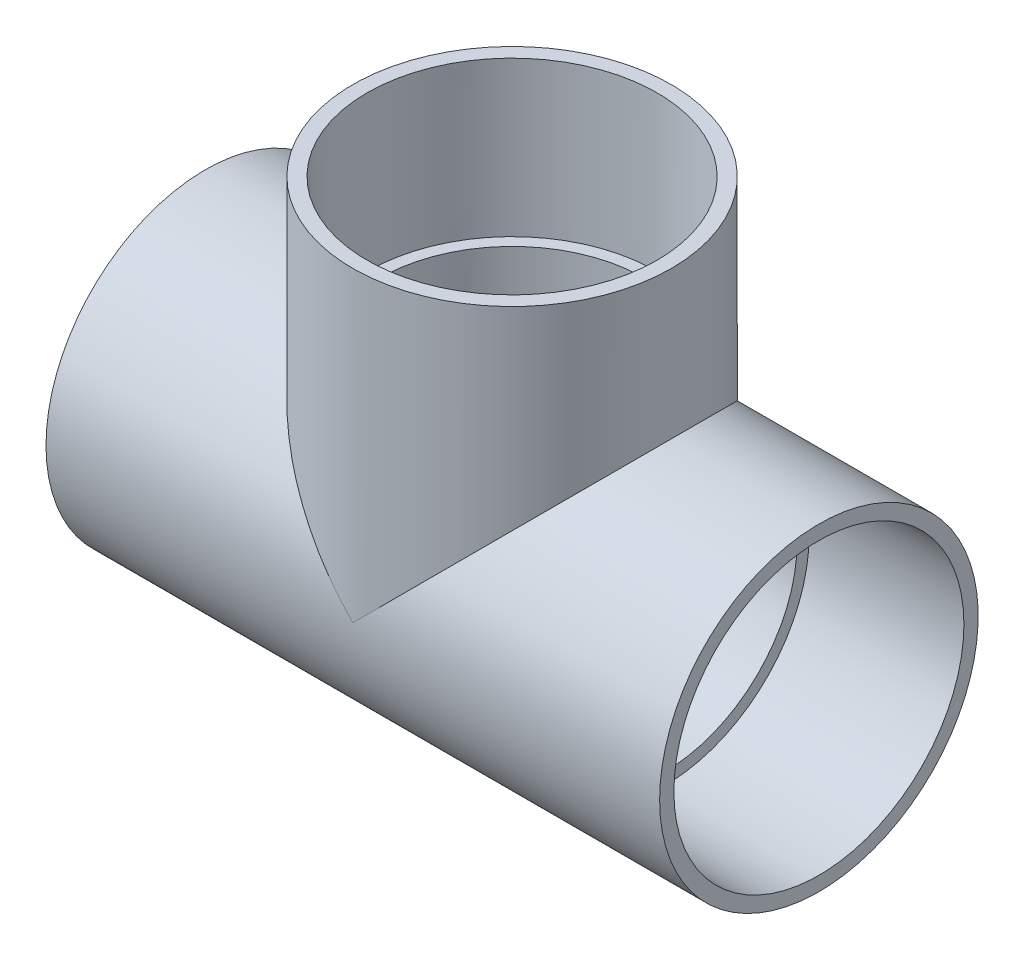
SolidWorks part; units mm, degrees
ref_plane "Front Plane" through (0, 0, 0) normal (0, 0, 1) x (1, 0, 0)
ref_plane "Top Plane" through (0, 0, 0) normal (0, 1, 0) x (1, 0, 0)
ref_plane "Right Plane" through (0, 0, 0) normal (1, 0, 0) x (0, 0, -1)
sketch "Sketch0" plane through (0, 0, 0) normal (0, 0, 1) x (1, 0, 0)
  line L0 (-178.5938, 0) -> (0, 0) construction
  line L1 (0, 0) -> (0, 178.5938) construction
  line L2 (-88.9, 0) -> (0, 0) construction
  line L3 (0, 0) -> (0, 88.9) construction
  line L4 (-178.5938, 92.71) -> (-178.5938, -92.71) construction
  line L5 (-88.9, 83.9978) -> (-178.5938, 84.4169) construction
  line L6 (-88.9, 83.9978) -> (-88.9, -83.9978) construction
  line L7 (-88.9, -83.9978) -> (-178.5938, -84.4169) construction
  line L8 (-178.5938, 84.4169) -> (-178.5938, -84.4169) construction
  line L9 (-92.71, 178.5938) -> (92.71, 178.5938) construction
  line L10 (-84.4169, 178.5938) -> (84.4169, 178.5938) construction
  line L11 (84.4169, 178.5938) -> (83.9978, 88.9) construction
  line L12 (83.9978, 88.9) -> (-83.9978, 88.9) construction
  line L13 (-83.9978, 88.9) -> (-84.4169, 178.5938) construction
  line L14 (-88.9, 77.0255) -> (-88.9, -77.0255) construction
  line L15 (-178.5938, 0) -> (-88.9, 0) construction
  line L16 (0, 178.5938) -> (0, 88.9) construction
  line L17 (0, 0) -> (88.9, 0) construction
  line L18 (-77.0255, 88.9) -> (77.0255, 88.9) construction
  line L19 (88.9, 0) -> (178.5938, 0) construction
  dimension "H" = 178.5938
  dimension "G" = 88.9
  dimension "M" = 185.42
  dimension "OD A" = 168.8338
  dimension "OD B" = 167.9956
  dimension "ID" = 154.051
  dimension "H3" = 178.5938
sketch "Sketch1" plane through (0, 0, 0) normal (0, 0, 1) x (1, 0, 0)
  line L0 (-178.5938, 0) -> (0, 0) construction
  line L1 (-178.5938, 0) -> (0, 0) construction
  line L2 (0, 0) -> (0, -92.71) construction
  line L3 (-178.5938, -92.71) -> (-88.9, -92.71)
  line L4 (-178.5938, -92.71) -> (-178.5938, -84.4169)
  line L5 (-178.5938, -84.4169) -> (-88.9, -83.9978)
  line L6 (-88.9, -92.71) -> (-88.9, -83.9978)
  line L7 (-88.9, -92.71) -> (0, -92.71) construction
  line L8 (178.5938, -84.4169) -> (88.9, -83.9978)
  line L9 (178.5938, -92.71) -> (178.5938, -84.4169)
  line L10 (88.9, -92.71) -> (88.9, -83.9978)
  line L11 (178.5938, -92.71) -> (88.9, -92.71)
revolve "Revolve1" add sketch "Sketch1" angle 360 about L1
sketch "Sketch2" plane through (0, 0, 0) normal (0, 0, 1) x (1, 0, 0)
  line L0 (84.4169, 178.5938) -> (83.9978, 88.9)
  line L1 (83.9978, 88.9) -> (92.71, 88.9)
  line L2 (92.71, 88.9) -> (92.71, 178.5938)
  line L3 (92.71, 178.5938) -> (84.4169, 178.5938)
  line L4 (0, 0) -> (0, 178.5938) construction
  line L5 (0, 0) -> (0, 178.5938) construction
revolve "Revolve2" add sketch "Sketch2" angle 360 about L5
sketch "Sketch3" plane through (-88.9, 0, 0) normal (1, 0, 0) x (0, 0, -1)
  circle A0 centre (0, 0) radius 77.0255
  circle A1 centre (0, 0) radius 92.71
sketch "Sketch4" plane through (-88.9, 0, 0) normal (1, 0, 0) x (0, 0, -1)
  circle A0 centre (0, 0) radius 92.71 construction
  circle A1 centre (0, 0) radius 92.71
extrude "Boss-Extrude1" add sketch "Sketch4" along normal up to vertex (177.8 mm away) up to point (88.9, 0, 0)
sketch "Sketch5" plane through (0, 88.9, 0) normal (0, -1, 0) x (1, 0, 0)
  circle A0 centre (0, 0) radius 92.71 construction
  circle A1 centre (0, 0) radius 92.71
extrude "Boss-Extrude2" add sketch "Sketch5" along normal up to vertex (88.9 mm away) up to point (0, 0, 0)
sketch "Sketch6" plane through (0, 0, 0) normal (0, 0, 1) x (1, 0, 0)
  line L0 (-178.5938, -84.4169) -> (-88.9, -83.9978)
  line L1 (-88.9, -83.9978) -> (-88.9, -77.0255)
  line L2 (-88.9, -77.0255) -> (88.9, -77.0255)
  line L3 (88.9, -83.9978) -> (88.9, 79.7728) construction
  line L4 (0, -77.0255) -> (0, 0) construction
  line L5 (88.9, -83.9978) -> (88.9, -77.0255)
  line L6 (178.5938, -84.4169) -> (178.5938, 84.4169) construction
  line L7 (178.5938, -92.71) -> (178.5938, 92.71) construction
  line L8 (178.5938, -84.4169) -> (178.5938, 0)
  line L9 (178.5938, 0) -> (-178.5938, 0)
  line L10 (-178.5938, 0) -> (-178.5938, -84.4169)
  line L11 (178.5938, -84.4169) -> (88.9, -83.9978)
revolve "Cut-Revolve1" cut sketch "Sketch6" angle 360 about L9
sketch "Sketch7" plane through (0, 0, 0) normal (0, 0, 1) x (1, 0, 0)
  line L0 (84.4169, 178.5938) -> (83.9978, 88.9)
  line L1 (83.9978, 88.9) -> (77.0255, 88.9)
  line L2 (77.0255, 88.9) -> (77.0255, 0)
  line L3 (0, 0) -> (88.9, 0) construction
  line L4 (77.0255, 0) -> (0, 0)
  line L5 (0, 0) -> (0, 178.5938)
  line L6 (-92.71, 178.5938) -> (92.71, 178.5938) construction
  line L7 (0, 178.5938) -> (84.4169, 178.5938)
revolve "Cut-Revolve2" cut sketch "Sketch7" angle 360 about L5
other "CPoint1" parameters "Diameter"=152.4, "StubLength"=152.4
ref_axis "Axis1" through (-98.9, 0, 0) along (1, 0, 0)
other "CPoint2" parameters "Diameter"=152.4, "StubLength"=152.4
ref_axis "Axis2" through (98.9, 0, 0) along (-1, 0, 0)
other "CPoint3" parameters "Diameter"=152.4, "StubLength"=152.4
ref_axis "Axis3" through (0, 98.9, 0) along (0, -1, 0)
other "RPoint1"
